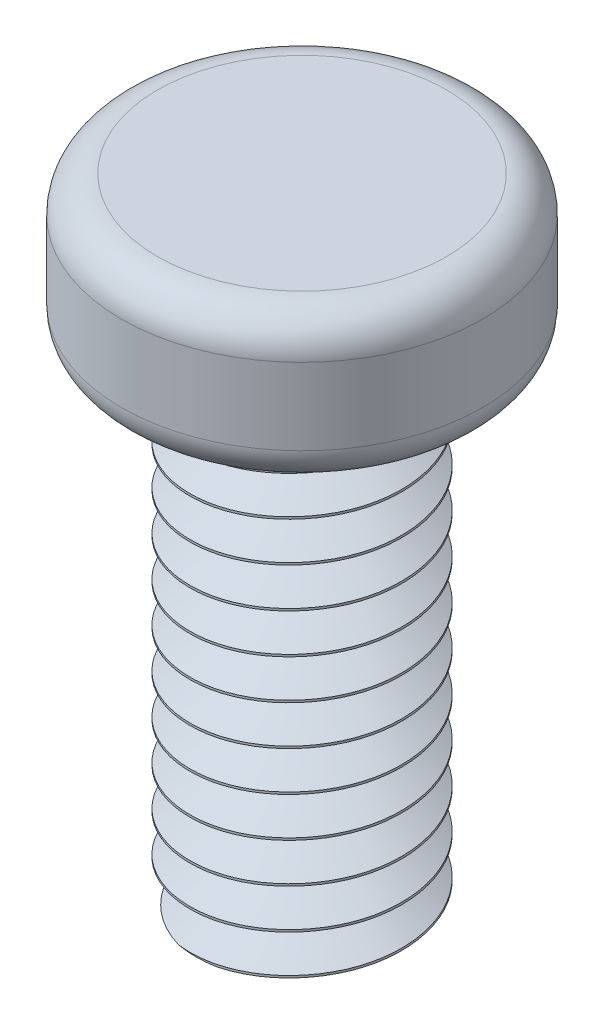
SolidWorks part; units mm, degrees
ref_plane "前视基准面" through (0, 0, 0) normal (0, 0, 1) x (1, 0, 0)
ref_plane "上视基准面" through (0, 0, 0) normal (0, 1, 0) x (1, 0, 0)
ref_plane "右视基准面" through (0, 0, 0) normal (1, 0, 0) x (0, 0, -1)
sketch "Sketch1" plane through (0, 0, 0) normal (0, 1, 0) x (1, 0, 0)
  circle A0 centre (0, 0) radius 2.5
  dimension "D1" = 5
extrude "Boss-Extrude1" add sketch "Sketch1" along normal blind 2.06
sketch "Sketch2" plane through (0, 0, 0) normal (0, -1, 0) x (1, 0, 0)
  circle A0 centre (0, 0) radius 1.47
  dimension "D1" = 2.94
extrude "Boss-Extrude2" add sketch "Sketch2" along normal blind 6.6
sketch "Sketch3" plane through (0, -6.6, 0) normal (0, -1, 0) x (1, 0, 0)
  circle A0 centre (0, 0) radius 1.47 construction
  circle A1 centre (0, 0) radius 1.47
curve "Helix/Spiral1" pitch 0.55 height 6.6 radius 1.47 centre (0, -6.6, 0) axis (0, 1, 0) start towards (0, 0, -1)
sketch "Sketch4" plane through (0, 0, 0) normal (1, 0, 0) x (0, 0, -1)
  line L0 (1.0197, -6.6) -> (1.47, -6.34)
  line L1 (-1.47, -6.6) -> (1.47, -6.6) construction
  line L2 (1.47, -6.6) -> (1.47, 0) construction
  line L3 (1.47, -6.34) -> (1.47, -6.86)
  line L4 (1.47, -6.86) -> (1.0197, -6.6)
  dimension "D1" = 0.52
  dimension "D2" = 0.52
  dimension "D3" = 0.52
sweep "Cut-Sweep1" cut profiles "Sketch4" path "Helix/Spiral1" align with end faces yes
fillet "Fillet4" radius 0.5 2 edges at (0, 0, 2.5) (0, 2.06, 2.5)
